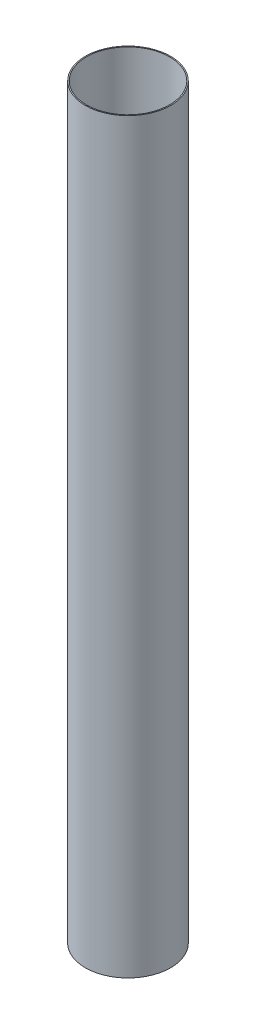
SolidWorks part; units mm, degrees
material "Wildman Fiberglass"
ref_plane "Front Plane" through (0, 0, 0) normal (0, 0, 1) x (1, 0, 0)
ref_plane "Top Plane" through (0, 0, 0) normal (0, 1, 0) x (1, 0, 0)
ref_plane "Right Plane" through (0, 0, 0) normal (1, 0, 0) x (0, 0, -1)
sketch "Sketch1" plane through (0, 0, 0) normal (0, 1, 0) x (1, 0, 0)
  circle A0 centre (0, 0) radius 49.53
  circle A1 centre (0, 0) radius 50.8
  dimension "D1" = 101.6
  dimension "D2" = 99.06
extrude "Boss-Extrude1" add sketch "Sketch1" along normal blind 889
equation "\"Length\"=35"
equation "\"D1@Boss-Extrude1\"=\"Length\""
